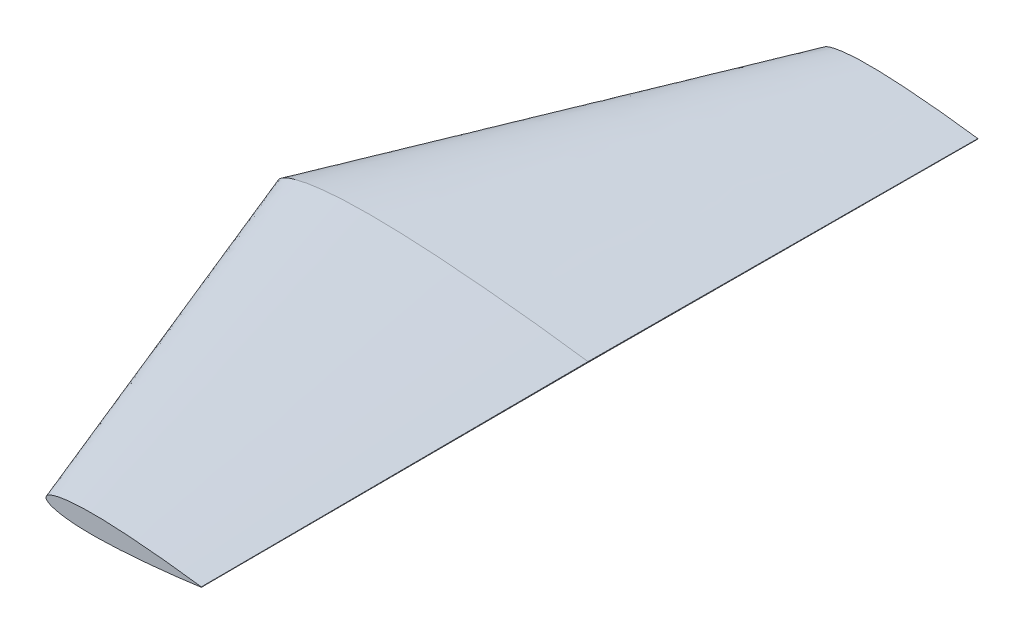
SolidWorks part; units mm, degrees
ref_plane "Front Plane" through (0, 0, 0) normal (0, 0, 1) x (1, 0, 0)
ref_plane "Top Plane" through (0, 0, 0) normal (0, 1, 0) x (1, 0, 0)
ref_plane "Right Plane" through (0, 0, 0) normal (1, 0, 0) x (0, 0, -1)
curve "Curve2"
  spline degree 3 poles (25.4, 0.032, 0) (25.3951, 0.0327, 0) (25.3753, 0.0355, 0) (25.3309, 0.0417, 0) (25.257, 0.052, 0) (25.1537, 0.0664, 0) (25.0214, 0.0846, 0) (24.8603, 0.1068, 0) (24.6708, 0.1326, 0) (24.4533, 0.1619, 0) (24.2084, 0.1946, 0) (23.9366, 0.2304, 0) (23.6385, 0.2691, 0) (23.3149, 0.3106, 0) (22.9666, 0.3545, 0) (22.5942, 0.4008, 0) (22.1987, 0.449, 0) (21.7811, 0.499, 0) (21.3422, 0.5505, 0) (20.8832, 0.6032, 0) (20.405, 0.6571, 0) (19.9089, 0.7116, 0) (19.3959, 0.7667, 0) (18.8673, 0.8219, 0) (18.3242, 0.8772, 0) (17.7681, 0.9321, 0) (17.2001, 0.9864, 0) (16.6216, 1.0399, 0) (16.0339, 1.0922, 0) (15.4384, 1.143, 0) (14.8366, 1.1921, 0) (14.2297, 1.2391, 0) (13.6193, 1.2836, 0) (13.0067, 1.3254, 0) (12.3935, 1.3642, 0) (11.7809, 1.3995, 0) (11.1705, 1.4311, 0) (10.5636, 1.4587, 0) (9.9618, 1.4818, 0) (9.3663, 1.5004, 0) (8.7786, 1.514, 0) (8.2001, 1.5224, 0) (7.632, 1.5254, 0) (7.0758, 1.5227, 0) (6.5327, 1.5144, 0) (6.0041, 1.5, 0) (5.491, 1.4798, 0) (4.9948, 1.4535, 0) (4.5166, 1.4212, 0) (4.0575, 1.3829, 0) (3.6185, 1.3388, 0) (3.2008, 1.2888, 0) (2.8052, 1.2334, 0) (2.4327, 1.1725, 0) (2.0841, 1.1064, 0) (1.7603, 1.0355, 0) (1.462, 0.96, 0) (1.1898, 0.8801, 0) (0.9445, 0.7962, 0) (0.7264, 0.7086, 0) (0.536, 0.6175, 0) (0.3737, 0.523, 0) (0.2396, 0.4254, 0) (0.1341, 0.3245, 0) (0.0574, 0.22, 0) (0.0105, 0.1114, 0) (-0.0051, 0, 0) (0.0105, -0.1114, 0) (0.0574, -0.22, 0) (0.1341, -0.3245, 0) (0.2396, -0.4254, 0) (0.3737, -0.523, 0) (0.536, -0.6175, 0) (0.7264, -0.7086, 0) (0.9445, -0.7962, 0) (1.1898, -0.8801, 0) (1.462, -0.96, 0) (1.7603, -1.0355, 0) (2.0841, -1.1064, 0) (2.4327, -1.1725, 0) (2.8052, -1.2334, 0) (3.2008, -1.2888, 0) (3.6185, -1.3388, 0) (4.0575, -1.3829, 0) (4.5166, -1.4212, 0) (4.9948, -1.4535, 0) (5.491, -1.4798, 0) (6.0041, -1.5, 0) (6.5327, -1.5144, 0) (7.0758, -1.5227, 0) (7.632, -1.5254, 0) (8.2001, -1.5224, 0) (8.7786, -1.514, 0) (9.3663, -1.5004, 0) (9.9618, -1.4818, 0) (10.5636, -1.4587, 0) (11.1705, -1.4311, 0) (11.7809, -1.3995, 0) (12.3935, -1.3642, 0) (13.0067, -1.3254, 0) (13.6193, -1.2836, 0) (14.2297, -1.2391, 0) (14.8366, -1.1921, 0) (15.4384, -1.143, 0) (16.0339, -1.0922, 0) (16.6216, -1.0399, 0) (17.2001, -0.9864, 0) (17.7681, -0.9321, 0) (18.3242, -0.8772, 0) (18.8673, -0.8219, 0) (19.3959, -0.7667, 0) (19.9089, -0.7116, 0) (20.405, -0.6571, 0) (20.8832, -0.6032, 0) (21.3422, -0.5505, 0) (21.7811, -0.499, 0) (22.1987, -0.449, 0) (22.5942, -0.4008, 0) (22.9666, -0.3545, 0) (23.3149, -0.3106, 0) (23.6385, -0.2691, 0) (23.9366, -0.2304, 0) (24.2084, -0.1946, 0) (24.4533, -0.1619, 0) (24.6708, -0.1326, 0) (24.8603, -0.1068, 0) (25.0214, -0.0846, 0) (25.1537, -0.0664, 0) (25.257, -0.052, 0) (25.3309, -0.0417, 0) (25.3753, -0.0355, 0) (25.3951, -0.0327, 0) (25.4, -0.032, 0) knots 0 0 0 0 0.000289 0.001156 0.002598 0.004612 0.007194 0.010336 0.014031 0.018272 0.023046 0.028343 0.03415 0.040454 0.047238 0.054489 0.062187 0.070314 0.078852 0.08778 0.097078 0.106722 0.116691 0.126961 0.137507 0.148306 0.159331 0.170556 0.181957 0.193504 0.205171 0.216932 0.228758 0.240621 0.252495 0.26435 0.276161 0.287898 0.299536 0.311047 0.322405 0.333584 0.344559 0.355306 0.3658 0.376018 0.385937 0.395538 0.404798 0.413699 0.422221 0.430349 0.438066 0.445357 0.452209 0.458612 0.464554 0.47003 0.475035 0.479569 0.483637 0.48725 0.490431 0.493219 0.495674 0.497891 0.5 0.502109 0.504326 0.506781 0.509569 0.51275 0.516363 0.520431 0.524965 0.52997 0.535446 0.541388 0.547791 0.554643 0.561934 0.569651 0.577779 0.586301 0.595202 0.604462 0.614063 0.623982 0.6342 0.644694 0.655441 0.666416 0.677595 0.688953 0.700464 0.712102 0.723839 0.73565 0.747505 0.759379 0.771242 0.783068 0.794829 0.806496 0.818043 0.829444 0.840669 0.851694 0.862493 0.873039 0.883309 0.893278 0.902922 0.91222 0.921148 0.929686 0.937813 0.945511 0.952762 0.959546 0.96585 0.971657 0.976954 0.981728 0.985969 0.989664 0.992806 0.995388 0.997402 0.998844 0.999711 1 1 1 1
sketch "Sketch1" plane through (0, 0, 0) normal (0, 0, 1) x (1, 0, 0)
  arc A0 (203.2, 0.256) -> (203.2, -0.256) centre (203.1165, 0) cw
  spline S1 degree 3 poles (203.2, 0.256) (203.1604, 0.2616) (203.0024, 0.2838) (202.3715, 0.372) (201.427, 0.5039) (200.1709, 0.6771) (198.8821, 0.8543) (197.366, 1.0608) (195.6262, 1.2952) (193.6669, 1.5566) (191.4925, 1.843) (189.1083, 2.1532) (186.5196, 2.4846) (182.6777, 2.9695) (178.5842, 3.4727) (174.2487, 3.9917) (170.7379, 4.4039) (167.0654, 4.8259) (163.2402, 5.2565) (159.271, 5.6927) (155.1671, 6.1332) (150.9381, 6.5751) (146.5939, 7.0173) (142.1445, 7.4566) (137.6006, 7.8915) (132.9725, 8.3191) (128.2711, 8.7378) (123.5074, 9.1443) (118.6925, 9.5368) (113.8378, 9.9127) (108.9544, 10.269) (104.0539, 10.6035) (99.1477, 10.9136) (92.6287, 11.2894) (86.139, 11.6065) (78.1265, 11.915) (71.8185, 12.0888) (65.6005, 12.1791) (61.0562, 12.2029) (56.6065, 12.1819) (52.262, 12.115) (48.0326, 12.0004) (43.9283, 11.8384) (39.9587, 11.628) (36.1328, 11.3696) (32.4599, 11.0635) (28.9483, 10.71) (25.6063, 10.3106) (22.4415, 9.867) (19.4615, 9.3798) (16.673, 8.8516) (14.0825, 8.2843) (11.696, 7.6799) (9.5188, 7.041) (7.5557, 6.3699) (5.8109, 5.6687) (4.2878, 4.9396) (2.9893, 4.184) (1.917, 3.4033) (1.0729, 2.5961) (0.4591, 1.7602) (0.0838, 0.8914) (-0.0408, 0) (0.0838, -0.8914) (0.4591, -1.7602) (1.0729, -2.5961) (1.917, -3.4033) (2.9893, -4.184) (4.2878, -4.9396) (5.8109, -5.6687) (7.5557, -6.3699) (9.5188, -7.041) (11.696, -7.6799) (14.0825, -8.2843) (16.673, -8.8516) (19.4615, -9.3798) (22.4415, -9.867) (25.6063, -10.3106) (28.9483, -10.71) (32.4599, -11.0635) (36.1328, -11.3696) (39.9587, -11.628) (43.9283, -11.8384) (48.0326, -12.0004) (52.262, -12.115) (56.6065, -12.1819) (61.0562, -12.2029) (65.6005, -12.1791) (71.8185, -12.0888) (79.7471, -11.8704) (87.7586, -11.532) (94.2472, -11.1961) (99.1477, -10.9136) (104.0539, -10.6035) (108.9544, -10.269) (113.8378, -9.9127) (118.6925, -9.5368) (123.5074, -9.1443) (128.2711, -8.7378) (132.9725, -8.3191) (137.6006, -7.8915) (142.1445, -7.4566) (146.5939, -7.0173) (150.9381, -6.5751) (155.1671, -6.1332) (159.271, -5.6927) (163.2402, -5.2565) (167.0654, -4.8259) (170.7379, -4.4039) (174.2487, -3.9917) (178.5842, -3.4727) (182.6777, -2.9695) (186.5196, -2.4846) (189.1083, -2.1532) (191.4925, -1.843) (193.6669, -1.5566) (195.6262, -1.2952) (197.366, -1.0608) (198.8821, -0.8543) (200.1709, -0.6771) (201.427, -0.5039) (202.3715, -0.372) (203.0024, -0.2838) (203.1604, -0.2616) (203.2, -0.256) knots 0 0 0 0 0.000289 0.001156 0.004612 0.007194 0.010336 0.014031 0.018272 0.023046 0.028343 0.03415 0.040454 0.047238 0.062187 0.070314 0.078852 0.08778 0.097078 0.106722 0.116691 0.126961 0.137507 0.148306 0.159331 0.170556 0.181957 0.193504 0.205171 0.216932 0.228758 0.240621 0.252495 0.26435 0.287898 0.299536 0.322405 0.333584 0.344559 0.355306 0.3658 0.376018 0.385937 0.395538 0.404798 0.413699 0.422221 0.430349 0.438066 0.445357 0.452209 0.458612 0.464554 0.47003 0.475035 0.479569 0.483637 0.48725 0.490431 0.493219 0.495674 0.497891 0.5 0.502109 0.504326 0.506781 0.509569 0.51275 0.516363 0.520431 0.524965 0.52997 0.535446 0.541388 0.547791 0.554643 0.561934 0.569651 0.577779 0.586301 0.595202 0.604462 0.614063 0.623982 0.6342 0.644694 0.655441 0.666416 0.677595 0.700464 0.723839 0.73565 0.747505 0.759379 0.771242 0.783068 0.794829 0.806496 0.818043 0.829444 0.840669 0.851694 0.862493 0.873039 0.883309 0.893278 0.902922 0.91222 0.921148 0.929686 0.937813 0.952762 0.959546 0.96585 0.971657 0.976954 0.981728 0.985969 0.989664 0.992806 0.995388 0.998844 0.999711 1 1 1 1
ref_plane "Plane1" through (0, 0, 254) normal (0, 0, 1) x (1, 0, 0)
sketch "Sketch2" plane through (0, 0, 254) normal (0, 0, 1) x (1, 0, 0)
  arc A0 (204.216, 0.128) -> (204.216, -0.128) centre (204.1984, 0) cw
  spline S1 degree 3 poles (204.216, 0.128) (204.1962, 0.1308) (204.1172, 0.1419) (203.8017, 0.186) (203.3295, 0.252) (202.7015, 0.3386) (202.0571, 0.4272) (201.299, 0.5304) (200.4291, 0.6476) (199.4494, 0.7783) (198.3623, 0.9215) (197.1701, 1.0766) (195.8758, 1.2423) (193.9548, 1.4847) (191.9081, 1.7363) (189.7404, 1.9959) (187.9849, 2.202) (186.1487, 2.4129) (184.2361, 2.6282) (182.2515, 2.8463) (180.1996, 3.0666) (178.0851, 3.2875) (175.9129, 3.5087) (173.6883, 3.7283) (171.4163, 3.9458) (169.1022, 4.1595) (166.7515, 4.3689) (164.3697, 4.5722) (161.9623, 4.7684) (159.5349, 4.9564) (157.0932, 5.1345) (154.643, 5.3018) (152.1899, 5.4568) (148.9303, 5.6447) (145.6855, 5.8032) (141.6792, 5.9575) (138.5253, 6.0444) (135.4162, 6.0896) (133.1441, 6.1015) (130.9193, 6.0909) (128.747, 6.0575) (126.6323, 6.0002) (124.5802, 5.9192) (122.5953, 5.814) (120.6824, 5.6848) (118.8459, 5.5317) (117.0901, 5.355) (115.4191, 5.1553) (113.8368, 4.9335) (112.3467, 4.6899) (110.9525, 4.4258) (109.6572, 4.1422) (108.464, 3.8399) (107.3754, 3.5205) (106.3938, 3.1849) (105.5214, 2.8344) (104.7599, 2.4698) (104.1107, 2.092) (103.5745, 1.7016) (103.1525, 1.298) (102.8455, 0.8801) (102.6579, 0.4457) (102.5956, 0) (102.6579, -0.4457) (102.8455, -0.8801) (103.1525, -1.298) (103.5745, -1.7016) (104.1107, -2.092) (104.7599, -2.4698) (105.5214, -2.8344) (106.3938, -3.1849) (107.3754, -3.5205) (108.464, -3.8399) (109.6572, -4.1422) (110.9525, -4.4258) (112.3467, -4.6899) (113.8368, -4.9335) (115.4191, -5.1553) (117.0901, -5.355) (118.8459, -5.5317) (120.6824, -5.6848) (122.5953, -5.814) (124.5802, -5.9192) (126.6323, -6.0002) (128.747, -6.0575) (130.9193, -6.0909) (133.1441, -6.1015) (135.4162, -6.0896) (138.5253, -6.0444) (142.4895, -5.9352) (146.4953, -5.766) (149.7396, -5.598) (152.1899, -5.4568) (154.643, -5.3018) (157.0932, -5.1345) (159.5349, -4.9564) (161.9623, -4.7684) (164.3697, -4.5722) (166.7515, -4.3689) (169.1022, -4.1595) (171.4163, -3.9458) (173.6883, -3.7283) (175.9129, -3.5087) (178.0851, -3.2875) (180.1996, -3.0666) (182.2515, -2.8463) (184.2361, -2.6282) (186.1487, -2.4129) (187.9849, -2.202) (189.7404, -1.9959) (191.9081, -1.7363) (193.9548, -1.4847) (195.8758, -1.2423) (197.1701, -1.0766) (198.3623, -0.9215) (199.4494, -0.7783) (200.4291, -0.6476) (201.299, -0.5304) (202.0571, -0.4272) (202.7015, -0.3386) (203.3295, -0.252) (203.8017, -0.186) (204.1172, -0.1419) (204.1962, -0.1308) (204.216, -0.128) knots 0 0 0 0 0.000289 0.001156 0.004612 0.007194 0.010336 0.014031 0.018272 0.023046 0.028343 0.03415 0.040454 0.047238 0.062187 0.070314 0.078852 0.08778 0.097078 0.106722 0.116691 0.126961 0.137507 0.148306 0.159331 0.170556 0.181957 0.193504 0.205171 0.216932 0.228758 0.240621 0.252495 0.26435 0.287898 0.299536 0.322405 0.333584 0.344559 0.355306 0.3658 0.376018 0.385937 0.395538 0.404798 0.413699 0.422221 0.430349 0.438066 0.445357 0.452209 0.458612 0.464554 0.47003 0.475035 0.479569 0.483637 0.48725 0.490431 0.493219 0.495674 0.497891 0.5 0.502109 0.504326 0.506781 0.509569 0.51275 0.516363 0.520431 0.524965 0.52997 0.535446 0.541388 0.547791 0.554643 0.561934 0.569651 0.577779 0.586301 0.595202 0.604462 0.614063 0.623982 0.6342 0.644694 0.655441 0.666416 0.677595 0.700464 0.723839 0.73565 0.747505 0.759379 0.771242 0.783068 0.794829 0.806496 0.818043 0.829444 0.840669 0.851694 0.862493 0.873039 0.883309 0.893278 0.902922 0.91222 0.921148 0.929686 0.937813 0.952762 0.959546 0.96585 0.971657 0.976954 0.981728 0.985969 0.989664 0.992806 0.995388 0.998844 0.999711 1 1 1 1
  point P0 (102.616, 0)
  point P4 (102.616, 0)
  dimension "D1" = 102.616
loft "Loft1" add profiles "Sketch1", "Sketch2" connector at (203.2, 0.256, 0) connector at (204.216, 0.128, 254)
mirror "Mirror1" about plane through (0, 0, 0) normal (0, 0, -1) of "Loft1"
